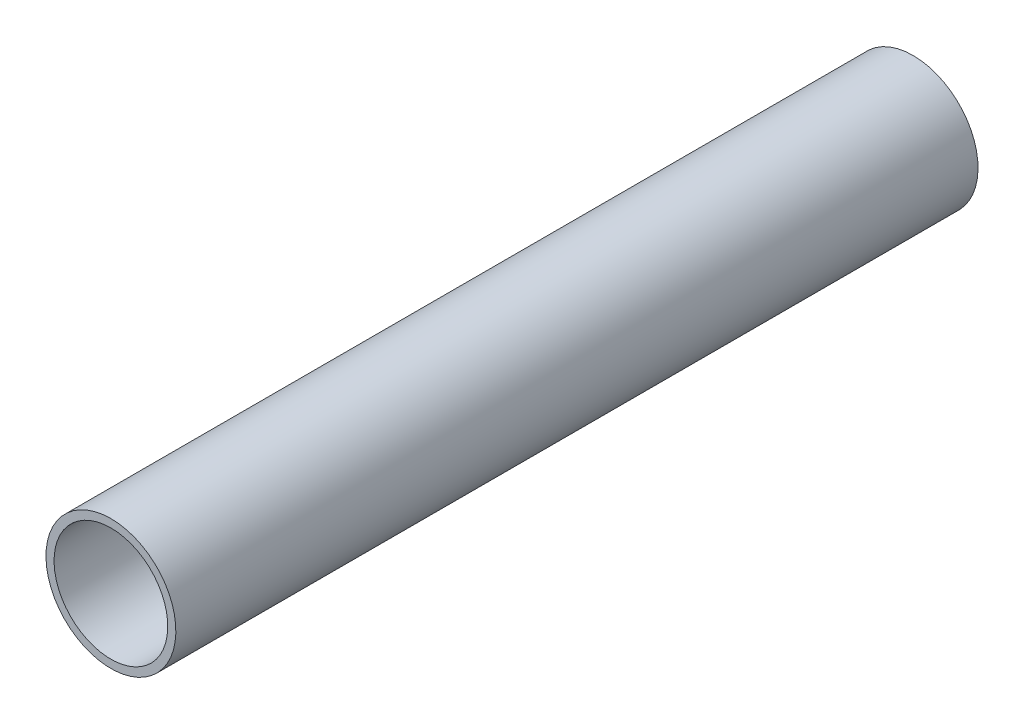
SolidWorks part; units mm, degrees
material "PE High Density"
ref_plane "Front Plane" through (0, 0, 0) normal (0, 0, 1) x (1, 0, 0)
ref_plane "Top Plane" through (0, 0, 0) normal (0, 1, 0) x (1, 0, 0)
ref_plane "Right Plane" through (0, 0, 0) normal (1, 0, 0) x (0, 0, -1)
sketch "Sketch2" plane through (0, 0, 0) normal (1, 0, 0) x (0, 0, -1)
  line L0 (17.9701, 0) -> (-700.436, 0) construction
  line L2 (-1000, 141.732) -> (1000, 141.732)
  line L3 (-1000, 141.732) -> (-1000, 161.925)
  line L4 (-1000, 161.925) -> (1000, 161.925)
  line L5 (1000, 141.732) -> (1000, 161.925)
  point P1 (811.1086, 0)
  point P2 (-17.9701, 103.3181)
  point P7 (0, 141.732)
  point P8 (148.4978, 141.732)
  point P9 (0, 0)
  point P10 (-718.4062, 0)
  point P11 (-7.7744, -14.4817)
  point P12 (12.6647, -7.0493)
  point P13 (-17.0649, 0)
  point P15 (898.1779, 0)
  point P16 (0, 0)
  point P17 (0, 0)
  point P18 (0, 0)
  point P19 (0, 0)
  point P20 (0, 0)
  dimension "D1" = 141.732
  dimension "D3" = 2000
  dimension "D2" = 161.925
revolve "Revolve1" add sketch "Sketch2" angle 360 about L0
ref_plane "Midplane" through (0, 0, 0) normal (0, 0, 1) x (1, 0, 0)
equation "\"ID\"= 11.160in"
equation "\"OD\"= 12.75in"
equation "\"Length\"= 2m"
equation "\"D3@Sketch2\"=\"Length\""
equation "\"D2@Sketch2\"=\"OD\"/2"
equation "\"D1@Sketch2\" = \"ID\" / 2"
